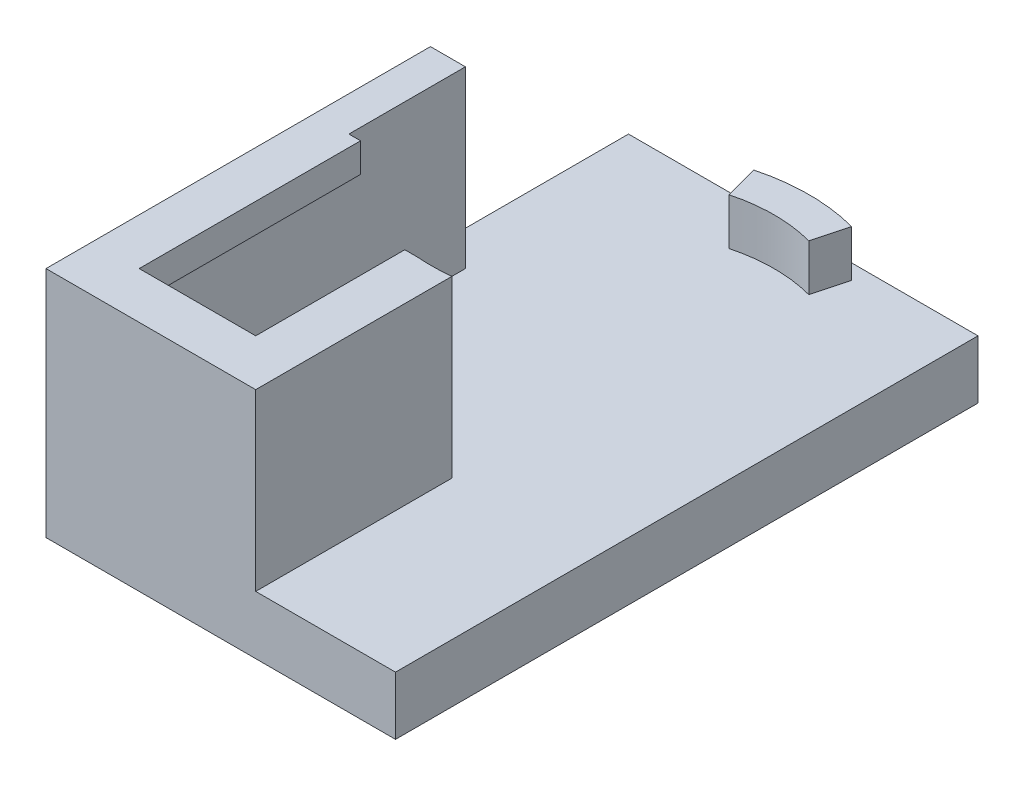
SolidWorks part; units mm, degrees
ref_plane "Front Plane" through (0, 0, 0) normal (0, 0, 1) x (1, 0, 0)
ref_plane "Top Plane" through (0, 0, 0) normal (0, 1, 0) x (1, 0, 0)
ref_plane "Right Plane" through (0, 0, 0) normal (1, 0, 0) x (0, 0, -1)
sketch "Sketch1" plane through (0, 0, 0) normal (0, 1, 0) x (1, 0, 0)
  line L1 (-22.5, 42.5) -> (22.5, 42.5)
  line L2 (-22.5, 42.5) -> (-22.5, -42.5)
  line L3 (-22.5, -42.5) -> (22.5, -42.5)
  line L4 (22.5, 42.5) -> (22.5, -42.5)
  line L5 (-22.5, 42.5) -> (22.5, -42.5) construction
  line L6 (-22.5, -42.5) -> (22.5, 42.5) construction
  point P0 (0, 0)
  dimension "D1" = 45
  dimension "D2" = 85
extrude "Boss-Extrude1" add sketch "Sketch1" along normal blind 100
shell "Shell1" thickness 5 removed face at (0, 100, 0)
sketch "Sketch2" plane through (0, 5, 0) normal (0, 1, 0) x (1, 0, 0)
  line L0 (-13.25, 0) -> (-13.25, -30)
  line L1 (-13.25, -30) -> (-1.25, -30)
  line L2 (-1.25, -30) -> (-1.25, -13.0576)
  line L3 (-16.25, 0) -> (-16.25, -33)
  line L4 (-16.25, -33) -> (1.75, -33)
  line L5 (1.75, -33) -> (1.75, -13.0576)
  line L6 (-13.25, 0) -> (-16.25, 0)
  line L7 (3.4294, 12.7985) -> (4.2058, 15.6963)
  line L8 (-4.2058, 15.6963) -> (-3.4294, 12.7985)
  line L19 (-1.25, -13.0576) -> (-1.25, -16.2019)
  line L20 (-13.25, -25) -> (-16.25, -25)
  line L21 (-16.25, -15) -> (-13.25, -15)
  circle A1 centre (0, 0) radius 16.25
  circle A2 centre (0, 0) radius 13.25
  dimension "D1" = 26.5
  dimension "D2" = 32.5
  dimension "D3" = 12
  dimension "D4" = 30
  dimension "D6" = 15
  dimension "D8" = 10
  dimension "D9" = 8
  dimension "D5" = 3
extrude "Boss-Extrude2" add sketch "Sketch2" along normal blind 15 contours A1 L2 L1 L0 L20 L3 L4 L5 | L21 L3 L20 L0 | A1 L3 L21 L0 | A2 L7 A1 L8 | L6 A1 L0 region at (-14.9656, 5, 10.4184) region at (-14.75, 5, 20) region at (-13.4965, 5, 27.5) region at (-14.46, 5, 3.5757) region at (0, 5, -14.6324)
sketch "Sketch4" plane through (-13.25, 0, 0) normal (1, 0, 0) x (0, 0, -1)
  line L0 (0, 5) -> (-30, 5) construction
  line L1 (-30, 20) -> (-10, 20)
  line L2 (-30, 20) -> (-30, 17.5)
  line L3 (-30, 17.5) -> (-10, 17.5)
  line L4 (-10, 20) -> (-10, 17.5)
  dimension "D1" = 12.5
  dimension "D2" = 20
extrude "Boss-Extrude3" add sketch "Sketch4" along normal blind 1
sketch "Sketch5" plane through (-1.25, 0, 0) normal (-1, 0, 0) x (0, 0, 1)
  line L0 (30, 20) -> (30, 5) construction
  line L1 (16.2019, 20) -> (30, 20)
  line L2 (16.2019, 20) -> (16.2019, 17.5)
  line L3 (16.2019, 17.5) -> (30, 17.5)
  line L4 (30, 20) -> (30, 17.5)
  line L5 (30, 5) -> (16.2019, 5) construction
  dimension "D1" = 12.5
extrude "Boss-Extrude4" add sketch "Sketch5" along normal blind 1
sketch "Sketch6" plane through (0, 0, 30) normal (0, 0, -1) x (-1, 0, 0)
  line L2 (12.25, 17.5) -> (2.25, 17.5)
  line L3 (12.25, 17.5) -> (12.25, 20)
  line L4 (12.25, 20) -> (2.25, 20)
  line L5 (2.25, 17.5) -> (2.25, 20)
extrude "Boss-Extrude5" add sketch "Sketch6" along normal blind 1
sketch "Sketch9" plane through (0, 20, 0) normal (0, 1, 0) x (1, 0, 0)
  line L1 (-5.0753, 17.3777) -> (5.4023, 17.3777)
  line L2 (-5.0753, 17.3777) -> (-5.0753, 11.055)
  line L3 (-5.0753, 11.055) -> (5.4023, 11.055)
  line L4 (5.4023, 17.3777) -> (5.4023, 11.055)
extrude "Cut-Extrude1" cut sketch "Sketch9" against normal blind 11
sketch "Sketch10" plane through (0, 5, 0) normal (0, 1, 0) x (1, 0, 0)
  line L1 (13.75, 17) -> (-16.25, 17)
  line L2 (13.75, 17) -> (13.75, -33)
  line L3 (13.75, -33) -> (-16.25, -33)
  line L4 (-16.25, 17) -> (-16.25, -33)
  line L5 (-25.747, -45.8391) -> (28.4861, -45.8391)
  line L6 (-25.747, -45.8391) -> (-25.747, 48.035)
  line L7 (-25.747, 48.035) -> (28.4861, 48.035)
  line L8 (28.4861, -45.8391) -> (28.4861, 48.035)
  dimension "D1" = 30
  dimension "D2" = 50
extrude "Cut-Extrude2" cut sketch "Sketch10" against normal through all and the other way through all
